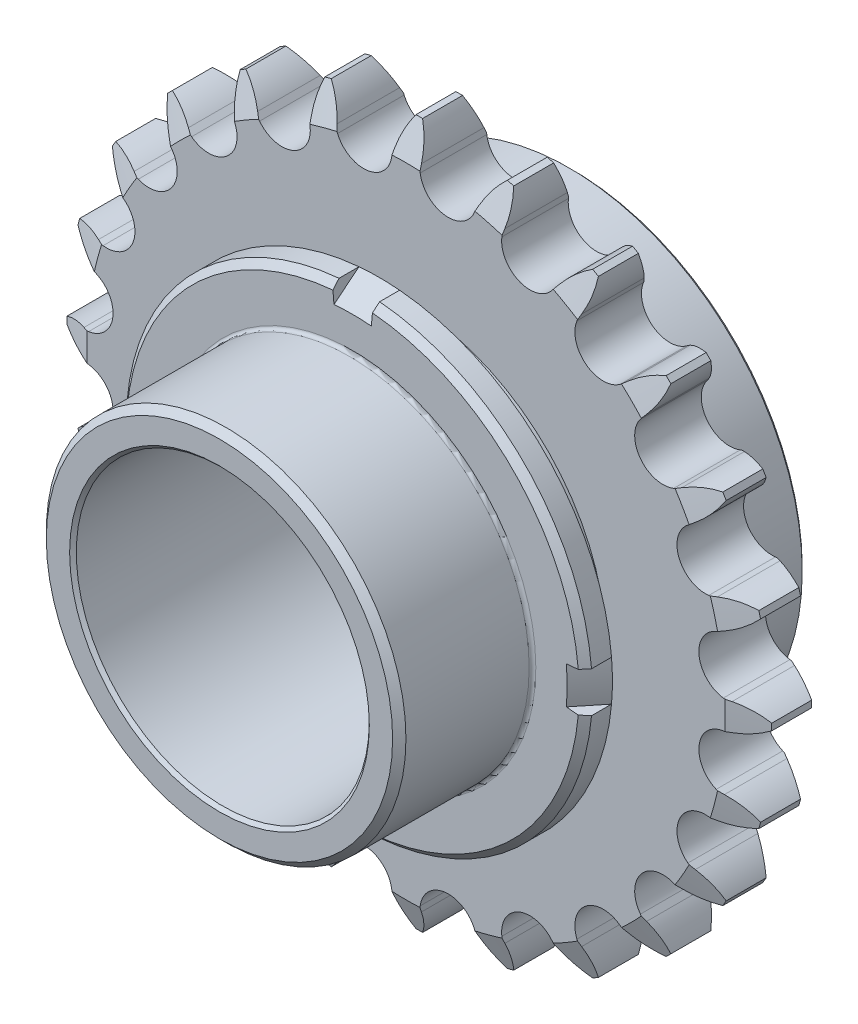
SolidWorks part; units mm, degrees
material "AISI 316 Annealed Stainless Steel Bar (SS)"
ref_plane "Front Plane" through (0, 0, 0) normal (0, 0, 1) x (1, 0, 0)
ref_plane "Top Plane" through (0, 0, 0) normal (0, 1, 0) x (1, 0, 0)
ref_plane "Right Plane" through (0, 0, 0) normal (1, 0, 0) x (0, 0, -1)
ref_axis "Axis1" through (0, 0, -22.65) along (0, 0, 1)
sketch "Sketch1" plane through (0, 0, 0) normal (0, 0, 1) x (1, 0, 0)
  line L0 (0, 0) -> (0, 48.6492) construction
  line L1 (-2.1352, 47.6492) -> (2.1352, 47.6492) construction
  line L2 (-2.1352, 47.6492) -> (-2.0213, 48.6492) construction
  line L3 (2.1352, 47.6492) -> (2.0213, 48.6492) construction
  line L4 (-2.0213, 48.6492) -> (2.0213, 48.6492) construction
  line L7 (-0.5, 52.9207) -> (0.5, 52.9207) construction
  circle A0 centre (0, 0) radius 48.6492 construction
  circle A1 centre (6.35, 48.233) radius 4.255 construction
  circle A2 centre (-6.35, 48.233) radius 4.255 construction
  circle A3 centre (0, 0) radius 44.3942 construction
  arc A4 (-2.0213, 48.6492) -> (-0.5, 52.9207) centre (7.9144, 47.5172) cw construction
  arc A5 (2.0213, 48.6492) -> (0.5, 52.9207) centre (-7.9144, 47.5172) ccw construction
  dimension "D1" = 13
  dimension "SprocketPitchDiameter" = 97.2985
  dimension "RollerDia" = 8.51
  dimension "D4" = 10
  dimension "ChainPitch" = 12.7
  dimension "D2" = 1
  dimension "D3" = 1
  dimension "D5" = 1
sketch "Sketch2" plane through (0, 0, 0) normal (0, 0, 1) x (1, 0, 0)
  circle A0 centre (0, 0) radius 44.3942 construction
  circle A1 centre (0, 0) radius 44.3942
extrude "Boss-Extrude1" add sketch "Sketch2" along normal mid plane 10
sketch "Sketch4" plane through (0, 0, 0) normal (0, 0, 1) x (1, 0, 0)
  line L0 (-0.5, 52.9207) -> (0.5, 52.9207) construction
  line L1 (-2.1352, 47.6492) -> (-2.0213, 48.6492) construction
  line L2 (2.1352, 47.6492) -> (2.0213, 48.6492) construction
  line L3 (-0.5, 52.9207) -> (0.5, 52.9207)
  line L4 (-2.1352, 47.6492) -> (-2.0213, 48.6492)
  line L5 (2.1352, 47.6492) -> (2.0213, 48.6492)
  circle A0 centre (0, 0) radius 44.3942 construction
  circle A1 centre (6.35, 48.233) radius 4.255 construction
  circle A2 centre (-6.35, 48.233) radius 4.255 construction
  arc A3 (2.0213, 48.6492) -> (0.5, 52.9207) centre (-7.9144, 47.5172) ccw construction
  arc A4 (-0.5, 52.9207) -> (-2.0213, 48.6492) centre (7.9144, 47.5172) ccw construction
  arc A5 (5.7946, 44.0144) -> (-5.7946, 44.0144) centre (0, 0) ccw
  arc A6 (2.1352, 47.6492) -> (5.7946, 44.0144) centre (6.35, 48.233) ccw
  arc A7 (-5.7946, 44.0144) -> (-2.1352, 47.6492) centre (-6.35, 48.233) ccw
  arc A8 (2.0213, 48.6492) -> (0.5, 52.9207) centre (-7.9144, 47.5172) ccw
  arc A9 (-0.5, 52.9207) -> (-2.0213, 48.6492) centre (7.9144, 47.5172) ccw
extrude "Boss-Extrude2" add sketch "Sketch4" along normal up to surface and the other way up to surface up to face at (44.3942, 0, 5) other way up to face at (44.3942, 0, -5)
pattern_circular "CirPattern1" count 24 over 360 about axis through (0, 0, 5) along (0, 0, -1) of "Boss-Extrude2"
sketch "Sketch5" plane through (0, 0, 0) normal (1, 0, 0) x (0, 0, -1)
  line L0 (0, 0) -> (-6, 0) construction
  line L1 (0, 52.9207) -> (0, 48.6492) construction
  line L2 (-6, 60.4207) -> (6, 60.4207)
  line L3 (-6, 60.4207) -> (-6, 45.4207)
  line L4 (-6, 45.4207) -> (6, 45.4207) construction
  line L5 (6, 60.4207) -> (6, 45.4207)
  line L6 (-6, 60.4207) -> (6, 45.4207) construction
  line L7 (-6, 45.4207) -> (6, 60.4207) construction
  line L8 (-6, 45.4207) -> (0, 60.4207)
  line L9 (6, 45.4207) -> (0, 60.4207)
  line L10 (0, 52.9207) -> (0, 48.6492) construction
  point P1 (0, 52.9207)
  dimension "D1" = 15
  dimension "D2" = 1
revolve "Cut-Revolve7" cut sketch "Sketch5" angle 360 about L0 region at (0, 55.4207, -4) region at (0, 55.4207, 4)
sketch "Sketch6" plane through (0, 0, 0) normal (0, 0, 1) x (1, 0, 0)
  circle A0 centre (0, 0) radius 35
  dimension "D1" = 70
extrude "Boss-Extrude3" add sketch "Sketch6" along normal blind 13 and the other way blind 20
sketch "Sketch7" plane through (0, 0, 0) normal (0, 0, 1) x (1, 0, 0)
  circle A0 centre (0, 0) radius 22
  dimension "D1" = 44
extrude "Cut-Extrude1" cut sketch "Sketch7" against normal through all both and the other way through all
sketch "Sketch9" plane through (0, 0, 13) normal (0, 0, 1) x (1, 0, 0)
  circle A2 centre (0, 0) radius 27
  circle A3 centre (0, 0) radius 27
  circle M2 centre (0, 0) radius 22
  dimension "D1" = 5
extrude "Boss-Extrude4" add sketch "Sketch9" along normal blind 20 contours A3 M2 region at (-26.2363, 0, 13)
chamfer "Chamfer1" distance 1 angle 45 3 edges at (27, 0, 33) (35, 0, 5) (35, 0, 13)
sketch "Sketch10" plane through (0, 0, 0) normal (1, 0, 0) x (0, 0, -1)
  line L1 (-5, 40) -> (-9, 40)
  line L2 (-5, 40) -> (-5, 30)
  line L3 (-5, 30) -> (-9, 30)
  line L4 (-9, 40) -> (-9, 30)
  line L5 (-5, 40) -> (-9, 30) construction
  line L6 (-5, 30) -> (-9, 40) construction
  line L7 (-5, 35) -> (-5, -35) construction
  line L8 (-6, 35) -> (-12, 35) construction
  point P0 (-7, 35)
  dimension "D1" = 4
  dimension "D2" = 10
revolve "Cut-Revolve8" cut sketch "Sketch10" angle 360 about axis through (0, 0, -20) along (0, 0, 1)
sketch "Sketch11" plane through (0, 0, 0) normal (1, 0, 0) x (0, 0, -1)
  line L0 (-9, 35) -> (-13, 32.1992)
  line L1 (-13, 35) -> (-13, -35) construction
  line L2 (-9, 35) -> (-13, 35)
  line L3 (-13, 35) -> (-13, 32.1992)
  dimension "D1" = 125
revolve "Cut-Revolve9" cut sketch "Sketch11" angle 10 mid plane about axis through (0, 0, -20) along (0, 0, 1)
pattern_circular "CirPattern2" count 4 over 360 about axis through (0, 0, -20) along (0, 0, 1) of "Cut-Revolve9"
chamfer "Chamfer2" distance 0.5 angle 45 3 edges at (22, 0, 33) (35, 0, -20) (22, 0, -20)
fillet "Fillet2" radius 0.5 2 edges at (35, 0, -5) (27, 0, 13)
equation "\"ChainPitch\"=12.7"
equation "\"ChainPitch@Sketch1\"=\"ChainPitch\""
equation "\"SprocketPitchDiameter@Sketch1\" = \"ChainPitch\" / sin ( 180 / \"NumberOfTeeth\" )"
equation "\"NumberOfTeeth\"= 24"
equation "\"D1@CirPattern1\"=\"NumberOfTeeth\""
